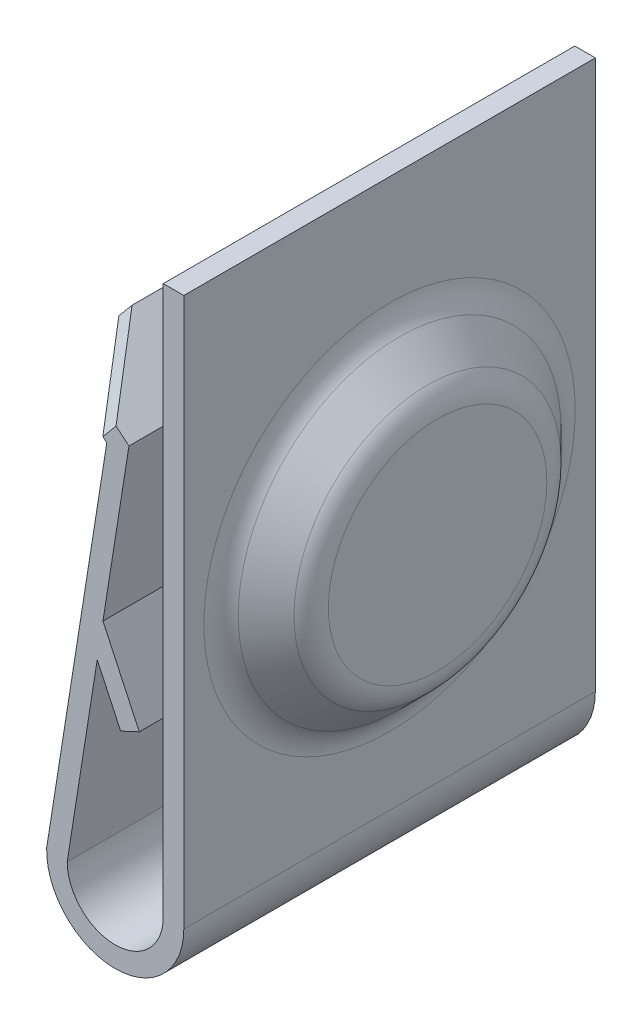
SolidWorks part; units mm, degrees
ref_plane "Front Plane" through (0, 0, 0) normal (0, 0, 1) x (1, 0, 0)
ref_plane "Top Plane" through (0, 0, 0) normal (0, 1, 0) x (1, 0, 0)
ref_plane "Right Plane" through (0, 0, 0) normal (1, 0, 0) x (0, 0, -1)
sketch "Sketch1" plane through (0, 0, 0) normal (0, 0, 1) x (1, 0, 0)
  line L0 (0, 0) -> (0, -8)
  line L1 (-1.4, -8) -> (-0.5, -2.3)
  line L3 (-0.5, -2.3) -> (-1.4543, -1.5)
  line L5 (0.3, 0) -> (0.3, -8)
  line L6 (-1.6997, -7.9744) -> (-0.8228, -2.4209)
  line L7 (-0.8228, -2.4209) -> (-1.6471, -1.7299)
  line L8 (-1.4543, -1.5) -> (-1.6471, -1.7299)
  line L9 (0, 0) -> (0.3, 0)
  line L10 (-0.9626, -5.2298) -> (-0.6212, -5.9611)
  line L11 (-0.6212, -5.9611) -> (-0.3494, -5.8342)
  line L12 (-0.3494, -5.8342) -> (-0.8789, -4.6999)
  line L13 (-0.8789, -4.6999) -> (-0.9626, -5.2298)
  arc A0 (0, -8) -> (-1.4, -8) centre (-0.7, -8) cw
  arc A1 (0.3, -8) -> (-1.6997, -7.9744) centre (-0.7, -8) cw
  point P2 (-1.9859, -9.7874)
  point P5 (-0.7, -8.7)
  point P12 (-1.9626, -9.6395)
  point P15 (-3.119, -6.0634)
  point P16 (-0.7128, -8.9999)
  point P25 (0, 0)
  point P26 (-1.6997, -7.8701)
  point P27 (-1.6997, -7.859)
  dimension "D1" = 121
  dimension "D2" = 1.4
  dimension "D3" = 8.7
  dimension "D4" = 7.2
  dimension "D5" = 0.5
  dimension "D6" = 6.4
  dimension "D8" = 0.7
  dimension "D9" = 146
  dimension "D10" = 0.3
  dimension "D11" = 4.3
  dimension "D7" = 0.3
extrude "Boss-Extrude1" add sketch "Sketch1" along normal blind 6 contours A1 L5 L9 L0 A0 L1 L3 L8 L7 L6 region at (0.15, -0.0922, 0)
chamfer "Chamfer1" distance 1 angle 45 2 edges at (-1.5507, -1.615, 0) (-1.5507, -1.615, 6)
sketch "Sketch2" plane through (0.3, 0, 0) normal (1, 0, 0) x (0, 0, -1)
  line L0 (-6, -9) -> (0, -9) construction
  line L1 (-6, 0) -> (-6, -8) construction
  circle A0 centre (-3, -4.3) radius 2.5
  circle A1 centre (-3, -4.3) radius 1.5
  point P7 (-3.1096, -4.364)
  dimension "D3" = 5
  dimension "D4" = 3
  dimension "D1" = 4.7
  dimension "D2" = 3
extrude "Boss-Extrude2" add sketch "Sketch2" along normal blind 0.7 contours A1 region at (0.3, -4.3, 3)
chamfer "Chamfer2" distance 1 angle 45 1 edges at (0.3, -4.3, 1.5)
fillet "Fillet1" radius 0.5 2 edges at (0.3, -4.3, 0.5) (1, -4.3, 1.2)
extrude "Boss-Extrude3" add sketch "Sketch1<3>" along normal blind 1 contours L11 L12 L1 L10 region at (-0.6966, -5.4194, 0)
sketch "Sketch1<3>" plane through (0, 0, 0) normal (0, 0, 1) x (1, 0, 0) same geometry as "Sketch1"
extrude "Boss-Extrude4" add sketch "Sketch1<4>" against normal blind 1 from surface contours L11 L12 L1 L10 region at (-0.6966, -5.4194, 0) starting at face at (-0.5404, -4.2923, 6)
sketch "Sketch1<4>" plane through (0, 0, 0) normal (0, 0, 1) x (1, 0, 0) same geometry as "Sketch1"
